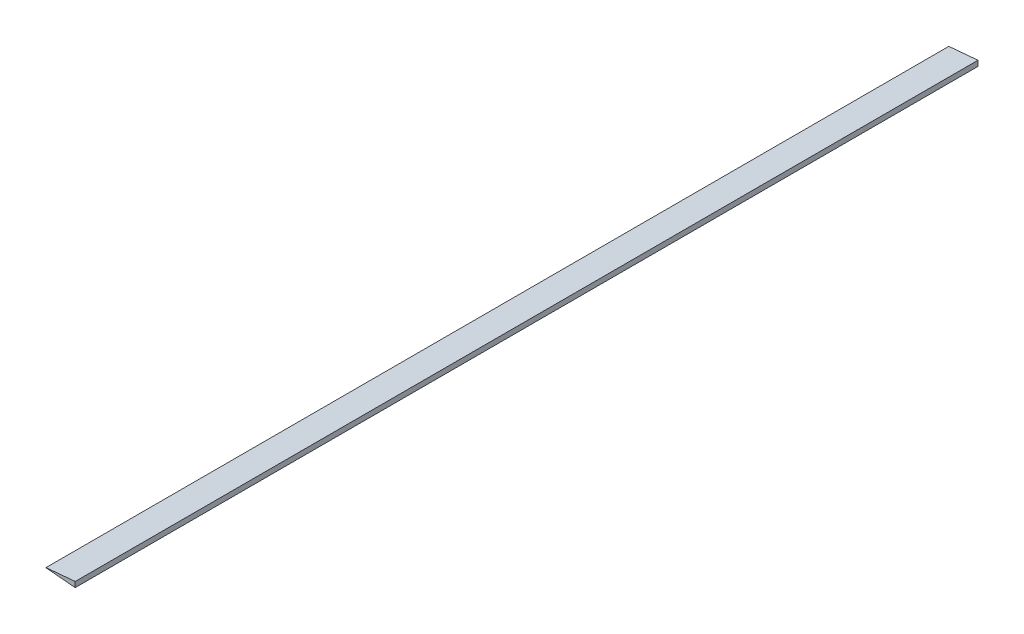
SolidWorks part; units mm, degrees
ref_plane "Front Plane" through (0, 0, 0) normal (0, 0, 1) x (1, 0, 0)
ref_plane "Top Plane" through (0, 0, 0) normal (0, 1, 0) x (1, 0, 0)
ref_plane "Right Plane" through (0, 0, 0) normal (1, 0, 0) x (0, 0, -1)
sketch "Sketch1" plane through (0, 0, 0) normal (0, 0, 1) x (1, 0, 0)
  line L0 (-63.8442, 2.5055) -> (-63.8442, -2.5055)
  line L1 (-91.206, 0.0862) -> (-91.206, -0.0862)
  spline S0 degree 3 poles (-63.8442, 2.5055) (-63.9466, 2.4983) (-65.4672, 2.391) (-68.3219, 2.1699) (-72.3106, 1.8515) (-76.0065, 1.5388) (-79.3694, 1.2416) (-82.3623, 0.966) (-84.9525, 0.7188) (-87.1115, 0.5063) (-88.8158, 0.3342) (-90.0466, 0.2075) (-90.7906, 0.1299) (-91.1227, 0.0949) (-91.206, 0.0862) knots 0 0 0 0 0.011212 0.166483 0.312686 0.448211 0.571563 0.681381 0.776452 0.855723 0.918312 0.963525 0.990856 1 1 1 1
  spline S1 degree 3 poles (-63.8442, -2.5055) (-63.9466, -2.4983) (-65.4672, -2.391) (-68.3219, -2.1699) (-72.3106, -1.8515) (-76.0065, -1.5388) (-79.3694, -1.2416) (-82.3623, -0.966) (-84.9525, -0.7188) (-87.1115, -0.5063) (-88.8158, -0.3342) (-90.0466, -0.2075) (-90.7906, -0.1299) (-91.1227, -0.0949) (-91.206, -0.0862) knots 0 0 0 0 0.011212 0.166483 0.312686 0.448211 0.571563 0.681381 0.776452 0.855723 0.918312 0.963525 0.990856 1 1 1 1
extrude "Boss-Extrude1" add sketch "Sketch1" along normal mid plane 845.8
